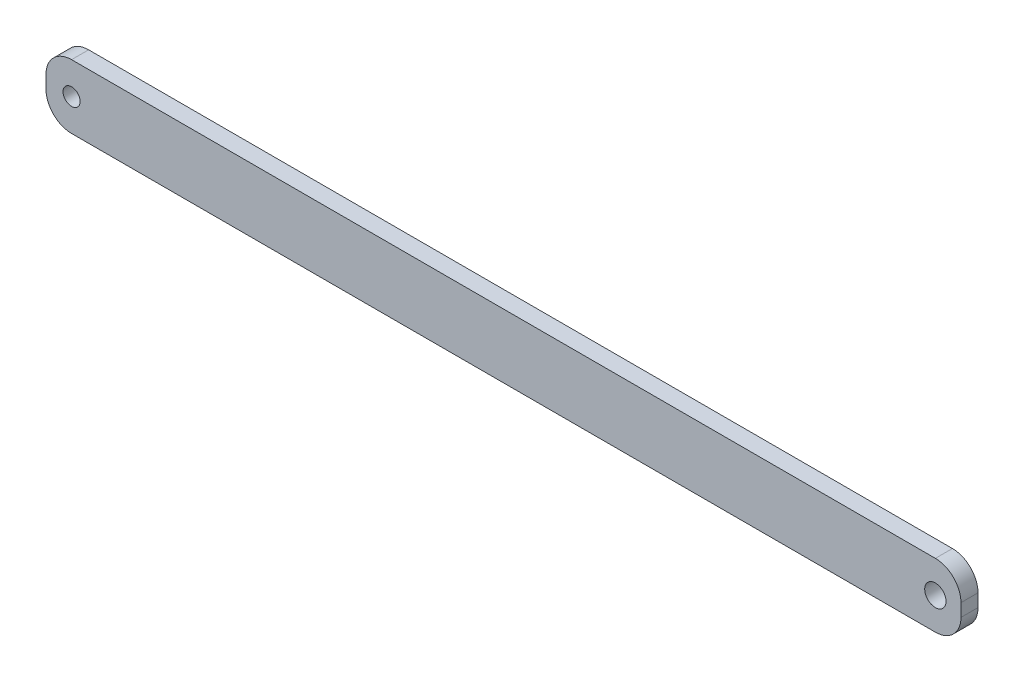
SolidWorks part; units mm, degrees
material "ABS PC"
ref_plane "Front Plane" through (0, 0, 0) normal (0, 0, 1) x (1, 0, 0)
ref_plane "Top Plane" through (0, 0, 0) normal (0, 1, 0) x (1, 0, 0)
ref_plane "Right Plane" through (0, 0, 0) normal (1, 0, 0) x (0, 0, -1)
sketch "Sketch1" plane through (0, 0, 0) normal (0, 0, 1) x (1, 0, 0)
  line L1 (7.62, 0) -> (264.922, 0)
  line L2 (0, 7.62) -> (0, 11.43)
  line L3 (7.62, 19.05) -> (264.922, 19.05)
  line L4 (272.542, 7.62) -> (272.542, 11.43)
  circle A0 centre (264.922, 9.525) radius 3.175
  circle A1 centre (7.62, 9.525) radius 2.54
  arc A2 (264.922, 0) -> (272.542, 7.62) centre (264.922, 7.62) ccw
  arc A3 (7.62, 0) -> (0, 7.62) centre (7.62, 7.62) cw
  arc A4 (264.922, 19.05) -> (272.542, 11.43) centre (264.922, 11.43) cw
  arc A5 (0, 11.43) -> (7.62, 19.05) centre (7.62, 11.43) cw
  point P13 (0, 0)
  dimension "D3" = 5.08
  dimension "D4" = 6.35
  dimension "D9" = 7.62
  dimension "D1" = 257.302
  dimension "D2" = 19.05
  dimension "D5" = 9.525
  dimension "D6" = 7.62
  dimension "D7" = 7.62
  dimension "D8" = 9.525
extrude "Boss-Extrude1" add sketch "Sketch1" along normal blind 5.08
